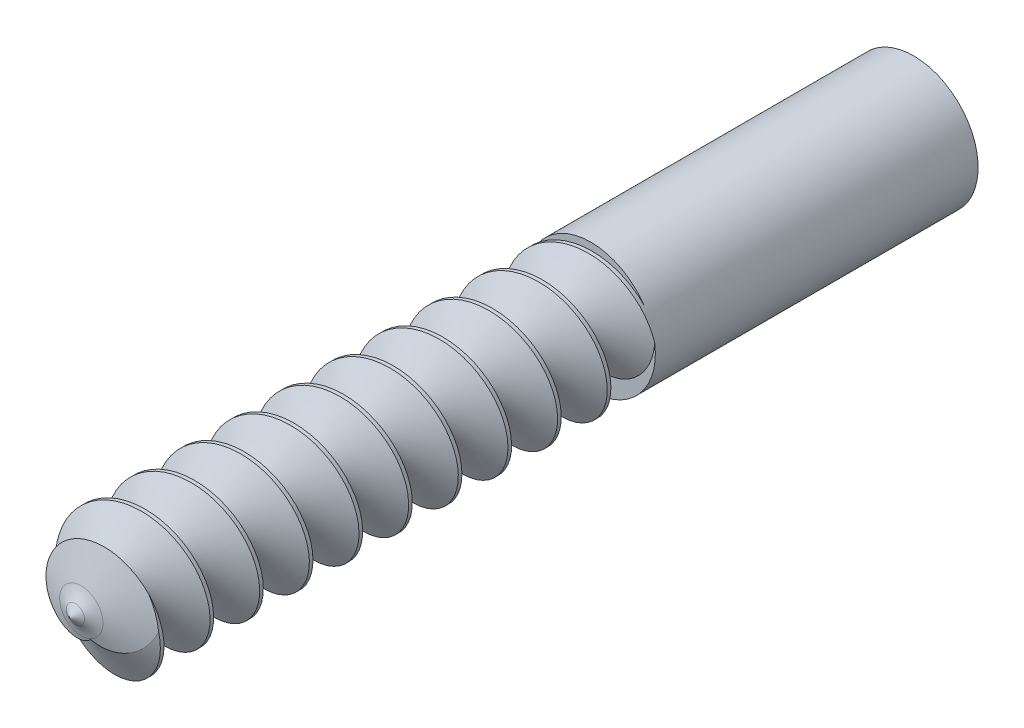
SolidWorks part; units mm, degrees
ref_plane "Front Plane" through (0, 0, 0) normal (0, 0, 1) x (1, 0, 0)
ref_plane "Top Plane" through (0, 0, 0) normal (0, 1, 0) x (1, 0, 0)
ref_plane "Right Plane" through (0, 0, 0) normal (1, 0, 0) x (0, 0, -1)
sketch "Sketch2" plane through (0, 0, 0) normal (0, 0, 1) x (1, 0, 0)
  circle A0 centre (0, 0) radius 6.5
  dimension "D1" = 13
extrude "Boss-Extrude1" add sketch "Sketch2" along normal blind 55
ref_plane "Plane1" through (0, 0, 60) normal (0, 0, 1) x (1, 0, 0)
sketch "Sketch4" plane through (0, 0, 60) normal (0, 0, 1) x (1, 0, 0)
  circle A0 centre (0, 0) radius 6.5 construction
  circle A1 centre (0, 0) radius 6.5
curve "Helix/Spiral1" pitch 5 height 70 radius 6.5 centre (0, 0, 60) axis (0, 0, -1) start towards (1, 0, 0)
ref_plane "Plane2" through (6.5, 0, 60) normal (0, -0.9926, -0.1215) x (-1, 0, 0)
sketch "Sketch5" plane through (6.5, 0, 60) normal (0, -0.9926, -0.1215) x (-1, 0, 0)
  line L0 (-0.0377, 2.6141) -> (-0.0377, -2.0359)
  line L1 (-0.0377, -2.0359) -> (4.2501, 0.2891)
  line L2 (4.2501, 0.2891) -> (-0.0377, 2.6141)
  dimension "D1" = 4.65
sweep "Cut-Sweep1" cut profiles "Sketch5" path "Helix/Spiral1" align with end faces yes
sketch "Sketch7" plane through (0, 0, 0) normal (0, 0, -1) x (-1, 0, 0)
  circle A0 centre (0, 0) radius 6.5
  dimension "D1" = 13
extrude "Boss-Extrude2" add sketch "Sketch7" along normal blind 30 and the other way blind 2.5
sketch "Sketch10" plane through (0, 0, 0) normal (0, 1, 0) x (1, 0, 0)
  line L0 (0, 0) -> (0, -67.302) construction
  line L2 (-7.6517, -52.1262) -> (-7.6517, -60.6768)
  line L3 (-7.6517, -60.6768) -> (0, -60.6768)
  line L4 (0, -60.6768) -> (0, -55)
  line L5 (0, -55) -> (-0.921, -54.3995)
  line L6 (-6.4382, -55) -> (2.1325, -55) construction
  line L7 (-2.1816, -53.809) -> (-7.6517, -52.1262)
  arc A0 (-0.921, -54.3995) -> (-2.1816, -53.809) centre (-3.6518, -58.588) ccw
  dimension "D1" = 5
revolve "Cut-Revolve3" cut sketch "Sketch10" angle 360 about L4
